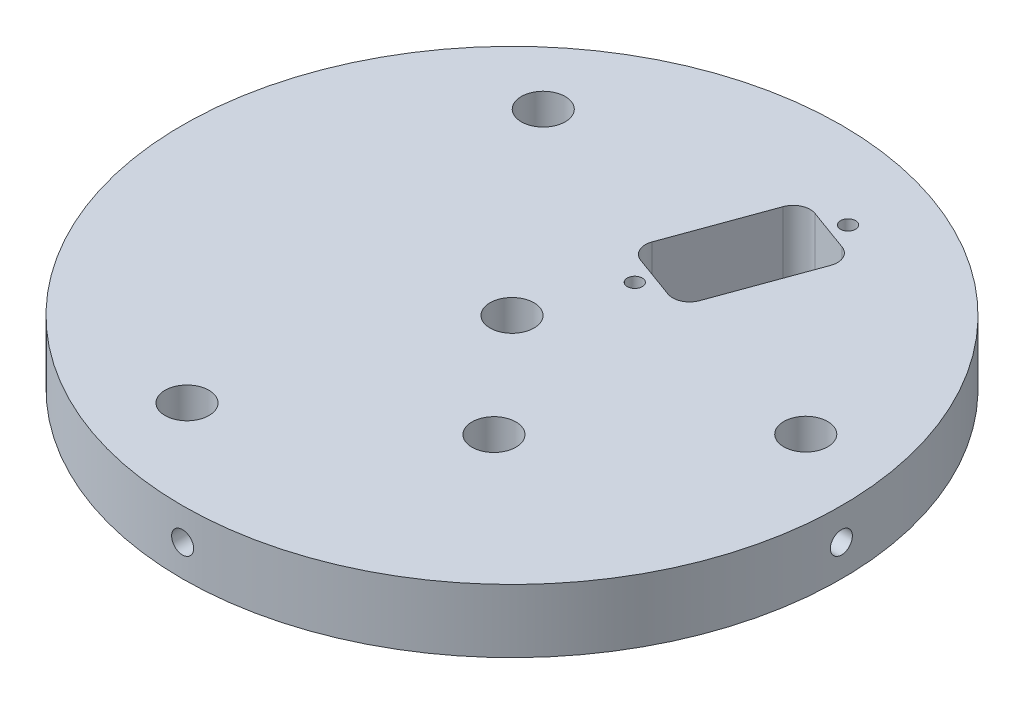
SolidWorks part; units mm, degrees
material "6061-T6 (SS)"
ref_plane "Front Plane" through (0, 0, 0) normal (0, 0, 1) x (1, 0, 0)
ref_plane "Top Plane" through (0, 0, 0) normal (0, 1, 0) x (1, 0, 0)
ref_plane "Right Plane" through (0, 0, 0) normal (1, 0, 0) x (0, 0, -1)
sketch "Sketch1" plane through (0, 0, 0) normal (0, 1, 0) x (1, 0, 0)
  line L0 (0, 0) -> (-50.3682, 60.0265)
  line L1 (0, 0) -> (50.3682, 60.0265)
  line L2 (0, 0) -> (0, 72.1431) construction
  circle A0 centre (0, 0) radius 78.359
  circle A1 centre (0, 0) radius 51.1048
  circle A2 centre (0, 0) radius 76.1746
  dimension "D1" = 156.718
  dimension "D2" = 102.2096
  dimension "D3" = 152.3492
  dimension "D4" = 80
extrude "Boss-Extrude1" add sketch "Sketch1" along normal blind 25.4 contours L2 A2 L1 A0 | L2 A1 L1 A2 | L2 A2 L1 A1 | L2 A0 L1 A2 | A2 L2 A1 L0 | A0 L2 A2 L0 | A2 L2 A0 L0 | A1 L2 A2 L0 region at (-22.4568, 0, 48.1587) region at (-40.1048, 0, -49.4238) region at (-33.0764, 0, 70.9325) region at (-48.8794, 0, -59.85)
ref_plane "Plane1" through (0, 12.7, 0) normal (0, 1, 0) x (1, 0, 0)
sketch "Sketch6" plane through (0, 25.4, 0) normal (0, 1, 0) x (1, 0, 0)
  circle A0 centre (0, 0) radius 49.5173
  dimension "D1" = 99.0346
extrude "Boss-Extrude5" add sketch "Sketch6" along normal blind 9.525
sketch "Sketch7" plane through (0, 0, 0) normal (0, -1, 0) x (1, 0, 0)
  circle A0 centre (0, 0) radius 49.5173
  dimension "D1" = 99.0346
extrude "Boss-Extrude6" add sketch "Sketch7" along normal blind 9.525
sketch "Sketch8" plane through (0, -9.525, 0) normal (0, -1, 0) x (1, 0, 0)
  circle A0 centre (0, 0) radius 46.99
  dimension "D1" = 93.98
ref_plane "Plane2" through (0, 0, -49.5173) normal (0, 0, -1) x (-1, 0, 0)
ref_plane "Plane5" through (0, 25.4, 0) normal (0, 1, 0) x (1, 0, 0)
ref_axis "Axis1" through (0, 0, 0) along (0, 1, 0)
ref_plane "Plane3" through (0, 34.925, 0) normal (0, 1, 0) x (1, 0, 0)
sketch "Sketch9" plane through (0, 34.925, 0) normal (0, 1, 0) x (1, 0, 0)
  line L0 (0, 0) -> (-26.8004, -73.6334) construction
  line L1 (0, 0) -> (32.0596, -38.2071) construction
  line L2 (0, 0) -> (0, -86.0416) construction
  circle A0 centre (0, 0) radius 3.3
  circle A1 centre (-13.031, -35.8023) radius 3.3
  circle A4 centre (14.1499, -16.8632) radius 3.3
  circle A5 centre (-24.4902, 29.1863) radius 3.3
  circle A6 centre (37.5212, 6.616) radius 3.3
  point P15 (-1.3039, -1.0954)
  point P18 (0, 0)
  dimension "D1" = 6.6
  dimension "D2" = 6.6
  dimension "D6" = 6.6
  dimension "D3" = 38.1
  dimension "D4" = 60
  dimension "D7" = 22.0133
  dimension "D8" = 20
extrude "Cut-Extrude6" cut sketch "Sketch9" against normal through all
sketch "Sketch10" plane through (0, 25.4, 0) normal (0, 1, 0) x (1, 0, 0)
  circle A0 centre (0, 0) radius 82.3228
extrude "Cut-Extrude7" cut sketch "Sketch10" against normal through all
hole_wizard "Tap Drill for #4-40 Tap1" positions "Sketch12" profile "Sketch13" hole size "#4-40" standard "ANSI Inch" end condition through all
sketch "Sketch12" plane through (0, 34.925, 0) normal (0, 1, 0) x (1, 0, 0)
  line L0 (0, 0) -> (18.0627, 49.6269) construction
  line L2 (0, 0) -> (-24.4902, 29.1863) construction
  circle A0 centre (0, 0) radius 14.3933 construction
  point P0 (4.9228, 13.5253)
  point P2 (13.4733, 37.0176)
  dimension "D3" = 28.7867
  dimension "D1" = 60
  dimension "D2" = 25
sketch "Sketch13" plane through (4.9228, 34.925, -13.5253) normal (1, 0, 0) x (0, 0, 1)
  line L0 (0, 0) -> (0, 9.525)
  line L1 (0, 9.525) -> (1.1303, 9.525)
  line L2 (1.1303, 9.525) -> (1.1303, 0)
  line L5 (1.1303, 0) -> (0, 0)
  line L11 (0, -6.35) -> (0, 107.95) construction
  dimension "Thru Hole Dia." = 2.2606
  dimension "Thru Hole Depth" = 9.525
sketch "Sketch14" plane through (0, 34.925, 0) normal (0, 1, 0) x (1, 0, 0)
  line L0 (4.9228, 13.5253) -> (13.4733, 37.0176) construction
  line L1 (12.1824, 16.0187) -> (17.4317, 30.4411)
  line L2 (8.9269, 14.5007) -> (2.4825, 16.8462)
  line L3 (15.9137, 33.6967) -> (9.4692, 36.0423)
  line L4 (0.9644, 20.1018) -> (6.2137, 34.5242)
  arc A0 (17.4317, 30.4411) -> (15.9137, 33.6967) centre (15.0449, 31.3099) ccw
  arc A1 (9.4692, 36.0423) -> (6.2137, 34.5242) centre (8.6005, 33.6555) ccw
  arc A2 (8.9269, 14.5007) -> (12.1824, 16.0187) centre (9.7956, 16.8875) ccw
  arc A3 (2.4825, 16.8462) -> (0.9644, 20.1018) centre (3.3512, 19.2331) cw
  point P0 (5.7047, 15.6734)
  dimension "D4" = 2.54
  dimension "D5" = 2.54
  dimension "D2" = 2.286
  dimension "D3" = 11.938
extrude "Cut-Extrude9" cut sketch "Sketch14" against normal through all
ref_plane "Plane6" through (49.5173, 0, 0) normal (1, 0, 0) x (0, 0, -1)
hole_wizard "Tap Drill for M4x0.7 Tap1" positions "Sketch16" profile "Sketch17" hole size "M4x0.7" standard "ANSI Metric"
sketch "Sketch16" plane through (49.5173, 0, 0) normal (1, 0, 0) x (0, 0, -1)
  line L1 (49.5173, 34.925) -> (-49.5173, 34.925) construction
  point P0 (0, 30.1625)
  dimension "D1" = 4.7625
sketch "Sketch17" plane through (49.5173, 30.1625, 0) normal (0, 1, 0) x (0, 0, -1)
  line L0 (0, 0) -> (0, 10.6434)
  line L1 (0, 10.6434) -> (1.65, 9.652)
  line L2 (1.65, 9.652) -> (1.65, 0)
  line L5 (1.65, 0) -> (0, 0)
  line L10 (0, 10.6434) -> (-1.65, 9.652) construction
  line L11 (0, -6.35) -> (0, 107.95) construction
  dimension "Hole Dia." = 3.3
  dimension "Hole Depth" = 9.652
  dimension "Drill Angle" = 118
pattern_circular "CirPattern1" count 4 over 360 about axis through (0, 34.925, 0) along (0, 1, 0) of "Tap Drill for M4x0.7 Tap1"
equation "\"AB_Coupler_OD_Length\"= 1in"
equation "\"AB_Coupling_Section_Length\"= 0.375in"
equation "\"AB_Coupler_Length\"= \"AB_Coupler_OD_Length\" + \"AB_Coupling_Section_Length\" * 2"
equation "\"Cutout_Angle\" = 60"
equation "\"AB_Coupler_Num_Screws\"= 4"
equation "\"Num_Cutouts\" = 4"
equation "\"AB_Coupler_OD\"= 4.024in"
equation "\"AB_Coupler_ID\"= 3.7in"
equation "\"AB_Coupler_Surface_Diameter\"= 3.899in"
equation "\"D2@Sketch1\"= \"Body_Tube_OD\""
equation "\"AB_Coupling_Screw_Diameter\"= 4.5mm"
equation "\"Aft_Section_Length\" = 32in"
equation "\"Mid_Coupler_Length\" = 12in"
equation "\"Lead_Screw_Dist\" = 2in"
equation "\"Lead_Screw_Diam\" = 0.375in"
equation "\"Lead_Screw_Length\" = \"Mid_Coupler_Length\" + 2*0.375in + 2*0.5in"
equation "\"Paddle_Pin_Offset\" = 0.25in"
equation "\"Paddle_Pin_Radius\" = 2.25*2/3in"
equation "\"D1@Sketch6\"=\"AB_Coupler_Surface_Diameter\""
equation "\"D1@Boss-Extrude5\"=\"AB_Coupling_Section_Length\""
equation "\"D1@Sketch7\"=\"AB_Coupler_Surface_Diameter\""
equation "\"D1@Boss-Extrude6\"=\"AB_Coupling_Section_Length\""
equation "\"D1@Sketch8\"=\"AB_Coupler_ID\""
equation "\"D3@Sketch9\"=\"Paddle_Pin_Radius\""
equation "\"Motor_OD\" = 54.4mm"
equation "\"AB_Paddle_Height\" = 0.375in"
equation "\"AB_Central_Bushing_Length\" = 0.75in"
equation "\"Paddle_Gear_OD\" = 3.2in"
equation "\"Fwd_BKHD_From_Top\" = 18in"
equation "\"Fin_Thickness\" = 0.118in"
equation "\"DB9_Hole_Dist\" = 25mm"
equation "\"D2@Sketch12\"=\"DB9_Hole_Dist\""
equation "\"Drive_Gear_OD\" = 1.7*2/3in"
equation "\"D3@Sketch12\"=\"Drive_Gear_OD\""
equation "\"DB9_Relief_Width\" = 0.47in"
equation "\"D3@Sketch14\"=\"DB9_Relief_Width\""
equation "\"DB9_Relief_Hole_Offset\" = 0.09in"
equation "\"D2@Sketch14\"=\"DB9_Relief_Hole_Offset\""
equation "\"D1@Sketch14\"=\"DB9_Relief_Hole_Offset\""
equation "\"Airbrakes_Wire_Hole_Dia\" = 0.25in"
equation "\"Airbrakes_Wire_Hole_Dist\" = 1.1*2/3in"
equation "\"Servo_Gear_Offset\" = 0.5in"
equation "\"Motor_Length\" = 401mm"
equation "\"Body_Tube_OD\"= 4.024in"
equation "\"Body_Tube_ID\"= 3.90in"
equation "\"Coupler_OD\" = 3.899in"
equation "\"Coupler_ID\" = 3.755in"
equation "\"Fwd_Section_Length\" = 20in"
equation "\"Mid_Section_Length\" = 4in"
equation "\"Aft_Upper_Tube_Length\" = 10in"
equation "\"Aft_Lower_Tube_Length\" = 18in"
equation "\"Nosecone_Coupler_Length\" = 5in"
equation "\"Avionics_Bulkhead_Thickness\" = 0.25in"
equation "\"Avionics_Bulkhead_Lip\" = 0.125in"
equation "\"Avionics_Board_Length\" = \"Mid_Coupler_Length\" - 2*\"Avionics_Bulkhead_Lip\""
equation "\"Lead_Screw_Hole_Diam\" = 0.386in"
equation "\"Centering_Ring_Cutout_Dia\"= 1in"
equation "\"D7@Sketch9\"=\"Drive_Gear_OD\"/2+.3"
equation "\"D1@Sketch16\"=.375/2"
